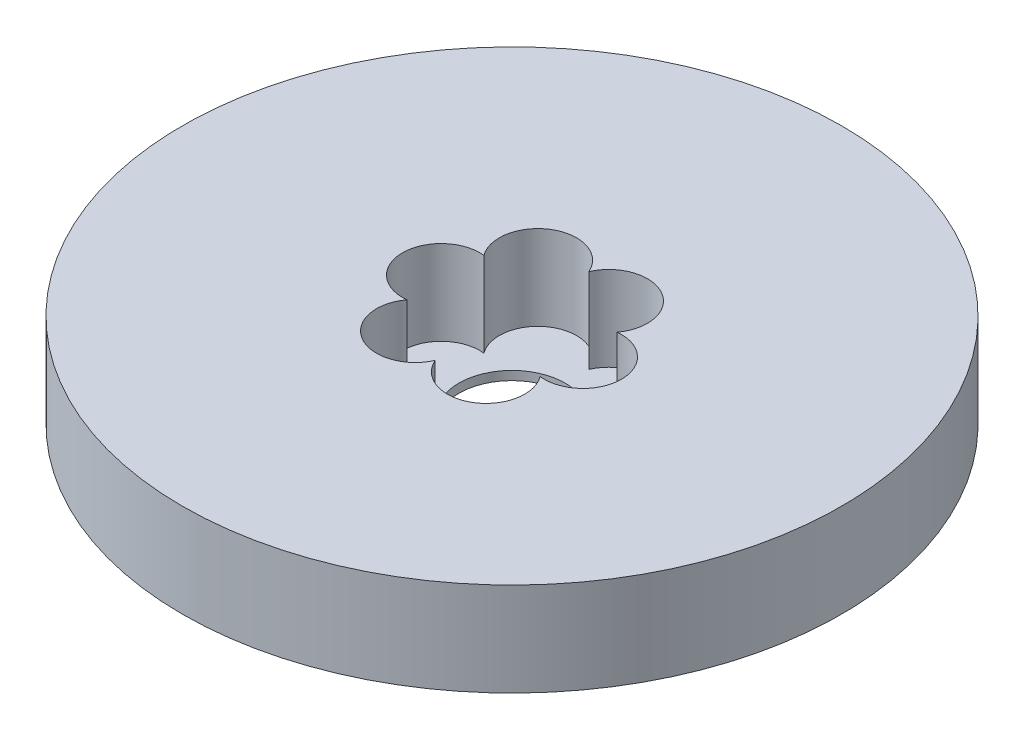
SolidWorks part; units mm, degrees
ref_plane "Front Plane" through (0, 0, 0) normal (0, 0, 1) x (1, 0, 0)
ref_plane "Top Plane" through (0, 0, 0) normal (0, 1, 0) x (1, 0, 0)
ref_plane "Right Plane" through (0, 0, 0) normal (1, 0, 0) x (0, 0, -1)
sketch "Sketch1" plane through (0, 0, 0) normal (0, 1, 0) x (1, 0, 0)
  circle A0 centre (0, 0) radius 77.5
  dimension "FLANGE_OD" = 155
extrude "Boss-Extrude1" add sketch "Sketch1" along normal blind 22
sketch "Sketch2" plane through (0, 0, 0) normal (0, 1, 0) x (1, 0, 0)
  circle A0 centre (0, 0) radius 12.5
  dimension "BORE_D" = 25
extrude "Cut-Extrude1" cut sketch "Sketch2" along normal through all
sketch "Sketch3" plane through (0, 22, 0) normal (0, 1, 0) x (1, 0, 0)
  circle A0 centre (0, 0) radius 16.6625 construction
  circle A1 centre (-16.6625, 0) radius 9.0945
  dimension "BOLT_D" = 18.1891
  dimension "BOLT_PCD" = 33.325
extrude "Cut-Extrude2" cut sketch "Sketch3" against normal blind 19.9155
pattern_circular "CirPattern1" count 6 over 360 about axis through (0, 0, 0) along (0, 1, 0) of "Cut-Extrude2"
